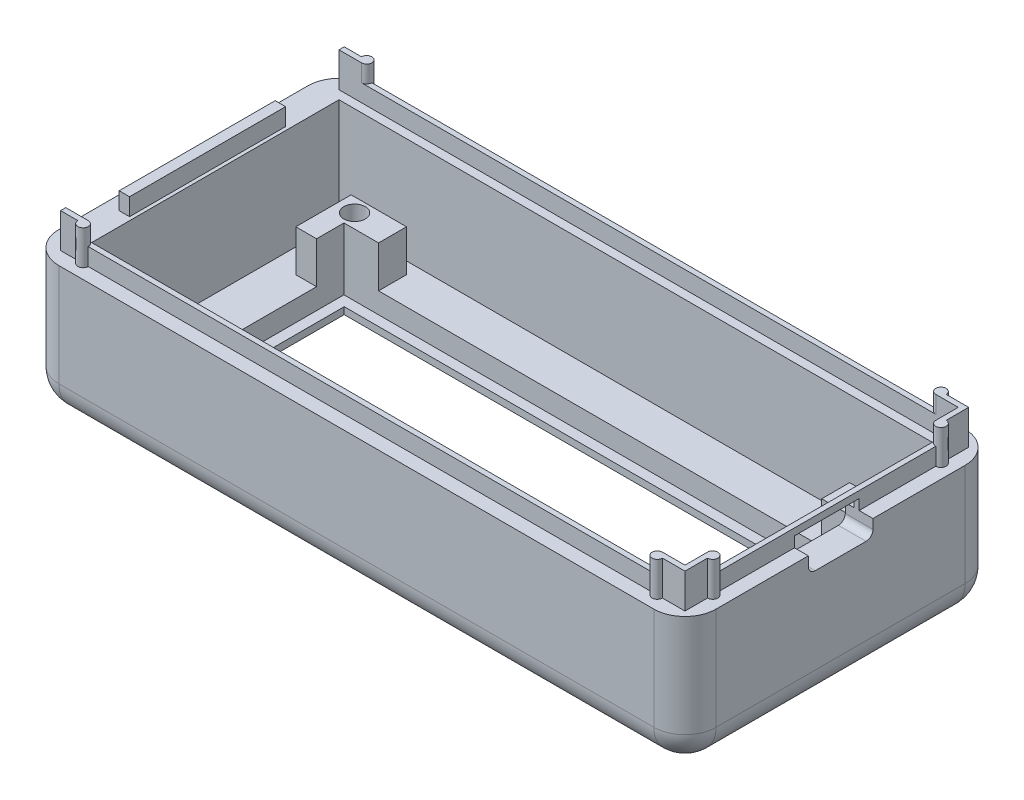
SolidWorks part; units mm, degrees
ref_plane "Спереди" through (0, 0, 0) normal (0, 0, 1) x (1, 0, 0)
ref_plane "Сверху" through (0, 0, 0) normal (0, 1, 0) x (1, 0, 0)
ref_plane "Справа" through (0, 0, 0) normal (1, 0, 0) x (0, 0, -1)
sketch "Эскиз1" plane through (0, 0, 0) normal (0, 1, 0) x (1, 0, 0)
  line L1 (0, 0) -> (95, 0)
  line L2 (0, 0) -> (0, -45)
  line L3 (0, -45) -> (95, -45)
  line L4 (95, 0) -> (95, -45)
  dimension "D1" = 45
  dimension "D2" = 95
extrude "Бобышка-Вытянуть1" add sketch "Эскиз1" along normal blind 19.3
shell "Оболочка1" thickness 4 removed face at (47.5, 19.3, 22.5)
fillet "Скругление1" radius 4.5 8 edges at (47.5, 0, 45) (95, 0, 22.5) (47.5, 0, 0) (0, 0, 22.5) (95, 9.65, 0) (95, 9.65, 45) (0, 9.65, 0) (0, 9.65, 45)
sketch "Эскиз2" plane through (0, 0, 0) normal (0, -1, 0) x (-1, 0, 0)
  line L0 (-47.5, -4.5) -> (-47.5, -40.5) construction
  line L1 (-83.025, -11.225) -> (-11.975, -11.225)
  line L2 (-83.025, -11.225) -> (-83.025, -33.775)
  line L3 (-83.025, -33.775) -> (-11.975, -33.775)
  line L4 (-11.975, -11.225) -> (-11.975, -33.775)
  line L5 (-4.5, -4.5) -> (-90.5, -4.5) construction
  line L6 (-90.5, -40.5) -> (-4.5, -40.5) construction
  line L7 (-90.5, -22.5) -> (-4.5, -22.5) construction
  line L8 (-90.5, -4.5) -> (-90.5, -40.5) construction
  line L9 (-4.5, -40.5) -> (-4.5, -4.5) construction
  point P17 (-83.025, -22.5)
  point P19 (-47.5, -33.775)
  dimension "D1" = 71.05
  dimension "D2" = 22.55
extrude "Вырез-Вытянуть1" cut sketch "Эскиз2" against normal blind 4.5
sketch "Эскиз6" plane through (0, 4, 0) normal (0, 1, 0) x (1, 0, 0)
  line L0 (11.975, -11.225) -> (11.975, -13.725)
  line L1 (11.975, -11.225) -> (11.975, -33.775) construction
  line L2 (11.975, -13.725) -> (7.475, -13.725)
  line L3 (7.475, -13.725) -> (7.475, -5.725)
  line L4 (7.475, -5.725) -> (15.475, -5.725)
  line L5 (15.475, -5.725) -> (15.475, -11.225)
  line L6 (83.025, -11.225) -> (11.975, -11.225) construction
  line L7 (15.475, -11.225) -> (11.975, -11.225)
  line L8 (11.975, -33.775) -> (11.975, -31.775)
  line L9 (11.975, -31.775) -> (7.475, -31.775)
  line L10 (7.475, -31.775) -> (7.475, -40.725)
  line L11 (7.475, -40.725) -> (15.475, -40.725)
  line L12 (15.475, -40.725) -> (15.475, -33.775)
  line L13 (11.975, -33.775) -> (83.025, -33.775) construction
  line L14 (15.475, -33.775) -> (11.975, -33.775)
  line L15 (47.5, -11.225) -> (47.5, -33.775) construction
  line L16 (11.975, -22.5) -> (83.025, -22.5) construction
  line L17 (83.025, -33.775) -> (83.025, -11.225) construction
  line L18 (87.525, -40.725) -> (79.525, -40.725)
  line L19 (79.525, -40.725) -> (79.525, -33.775)
  line L20 (79.525, -33.775) -> (83.025, -33.775)
  line L21 (83.025, -33.775) -> (83.025, -31.775)
  line L22 (83.025, -31.775) -> (87.525, -31.775)
  line L23 (87.525, -31.775) -> (87.525, -40.725)
  line L24 (79.525, -5.725) -> (79.525, -11.225)
  line L25 (79.525, -11.225) -> (83.025, -11.225)
  line L26 (83.025, -11.225) -> (83.025, -13.725)
  line L27 (83.025, -13.725) -> (87.525, -13.725)
  line L28 (87.525, -13.725) -> (87.525, -5.725)
  line L29 (87.525, -5.725) -> (79.525, -5.725)
  dimension "D1" = 8
  dimension "D2" = 8
  dimension "D3" = 4.5
  dimension "D4" = 4.5
  dimension "D5" = 35
  dimension "D6" = 8
  dimension "D7" = 2
  dimension "D8" = 5.5
extrude "Бобышка-Вытянуть3" add sketch "Эскиз6" along normal blind 6
sketch "Эскиз7" plane through (0, 10, 0) normal (0, 1, 0) x (1, 0, 0)
  line L2 (47.5, -11.225) -> (47.5, -33.775) construction
  line L3 (79.525, -11.225) -> (15.475, -11.225) construction
  line L4 (15.475, -33.775) -> (79.525, -33.775) construction
  line L5 (11.975, -22.75) -> (83.025, -22.75) construction
  line L6 (11.975, -13.725) -> (11.975, -31.775) construction
  line L7 (83.025, -31.775) -> (83.025, -13.725) construction
  line L10 (11.975, -13.725) -> (11.975, -11.225) construction
  line L11 (11.975, -11.225) -> (15.475, -11.225) construction
  line L12 (11.975, -31.775) -> (7.475, -31.775) construction
  line L13 (11.975, -33.775) -> (11.975, -31.775) construction
  circle A0 centre (9.975, -7.725) radius 1.55
  circle A1 centre (85.025, -7.725) radius 1.55
  circle A2 centre (9.975, -38.725) radius 1.55
  circle A3 centre (85.025, -38.725) radius 1.55
  point P28 (11.975, -32.775)
  dimension "D1" = 3.1
  dimension "D4" = 3.1
  dimension "D2" = 3.5
  dimension "D3" = 2
  dimension "D5" = 6.95
  dimension "D6" = 2
extrude "Вырез-Вытянуть2" cut sketch "Эскиз7" against normal blind 4
sketch "Эскиз8" plane through (0, 19.3, 0) normal (0, 1, 0) x (1, 0, 0)
  line L0 (91, -4) -> (4, -4) construction
  line L1 (2, -5.25) -> (2, -2)
  line L2 (4, -4) -> (4, -41) construction
  line L3 (47.5, -4) -> (47.5, -41) construction
  line L4 (91, -4) -> (4, -4) construction
  line L5 (4, -41) -> (91, -41) construction
  line L6 (4, -22.5) -> (91, -22.5) construction
  line L7 (4, -4) -> (4, -41) construction
  line L8 (91, -41) -> (91, -4) construction
  line L9 (2, -2) -> (5.25, -2)
  line L10 (2.75, -6) -> (2.75, -2.75)
  line L11 (2.75, -2.75) -> (6, -2.75)
  line L12 (92.25, -6) -> (92.25, -2.75)
  line L13 (92.25, -2.75) -> (89, -2.75)
  line L14 (93, -2) -> (89.75, -2)
  line L15 (93, -5.25) -> (93, -2)
  line L16 (93, -39.75) -> (93, -43)
  line L17 (93, -43) -> (89.75, -43)
  line L18 (92.25, -42.25) -> (89, -42.25)
  line L19 (92.25, -39) -> (92.25, -42.25)
  line L20 (2.75, -42.25) -> (6, -42.25)
  line L21 (2.75, -39) -> (2.75, -42.25)
  line L22 (2, -43) -> (5.25, -43)
  line L23 (2, -39.75) -> (2, -43)
  line L24 (2, -6.75) -> (2, -38.25)
  line L25 (2.75, -39) -> (2.75, -6)
  line L26 (6.75, -2) -> (88.25, -2)
  line L27 (89, -2.75) -> (6, -2.75)
  line L28 (92.25, -39) -> (92.25, -6)
  line L29 (93, -6.75) -> (93, -38.25)
  line L30 (89, -42.25) -> (6, -42.25)
  line L31 (6.75, -43) -> (88.25, -43)
  line L32 (2.75, -2.75) -> (2.75, -2)
  line L33 (2.75, -42.25) -> (2.75, -43)
  circle A0 centre (2, -6) radius 0.75
  circle A1 centre (6, -2) radius 0.75
  circle A2 centre (89, -2) radius 0.75
  circle A3 centre (93, -6) radius 0.75
  circle A4 centre (93, -39) radius 0.75
  circle A5 centre (89, -43) radius 0.75
  circle A6 centre (6, -43) radius 0.75
  circle A7 centre (2, -39) radius 0.75
  dimension "D1" = 1.5
  dimension "D4" = 1.5
  dimension "D2" = 2
  dimension "D3" = 2
  dimension "D5" = 2
  dimension "D6" = 2
extrude "Бобышка-Вытянуть5" add sketch "Эскиз8" along normal blind 5 contours A6 | A1 | A2 | L12 A3 L15 L14 A2 L13 | A3 | A4 | A5 L17 L16 A4 L19 L18 | A5 | L22 A6 L20 L33 | A1 L9 L32 L11 region at (4.0857, 19.3, 2.3875) region at (6, 19.3, 2) region at (4.0857, 19.3, 42.6125) region at (89.5703, 19.3, 2.5703) region at (89, 19.3, 2) region at (6, 19.3, 43) region at (90.625, 19.3, 42.3066) region at (89, 19.3, 43) region at (93, 19.3, 6) region at (93, 19.3, 39)
extrude "Бобышка-Вытянуть6" add sketch "Эскиз8<4>" along normal blind 2.5 contours L27 A2 L26 A1 | A4 L29 A3 L28 | L30 A6 L31 A5 region at (47.5, 19.3, 2.3758) region at (47.5, 19.3, 42.6242) region at (92.6229, 19.3, 22.5)
sketch "Эскиз8<4>" plane through (0, 19.3, 0) normal (0, 1, 0) x (1, 0, 0) same geometry as "Эскиз8"
sketch "Эскиз9" plane through (0, 19.3, 0) normal (0, 1, 0) x (1, 0, 0)
  line L0 (0, -4.5) -> (0, -40.5) construction
  line L1 (2, -11.225) -> (3.5, -11.225)
  line L2 (2, -11.225) -> (2, -33.775)
  line L3 (2, -33.775) -> (3.5, -33.775)
  line L4 (3.5, -11.225) -> (3.5, -33.775)
  line L5 (79.525, -11.225) -> (15.475, -11.225) construction
  line L6 (15.475, -33.775) -> (79.525, -33.775) construction
  dimension "D1" = 2
  dimension "D2" = 1.5
extrude "Бобышка-Вытянуть7" add sketch "Эскиз9" along normal blind 2.5
sketch "Эскиз10" plane through (0, 10, 0) normal (0, 1, 0) x (1, 0, 0)
  line L0 (87.525, -13.725) -> (87.525, -5.725) construction
  line L1 (10.475, -9.7624) -> (84.525, -9.7624)
  line L2 (10.475, -9.7624) -> (10.475, -36.725)
  line L3 (10.475, -36.725) -> (84.525, -36.725)
  line L4 (84.525, -9.7624) -> (84.525, -36.725)
  line L5 (79.525, -40.725) -> (87.525, -40.725) construction
  line L6 (79.525, -11.225) -> (83.025, -11.225) construction
  line L7 (7.475, -5.725) -> (7.475, -13.725) construction
  dimension "D1" = 3
  dimension "D2" = 4
  dimension "D3" = 1.4626
  dimension "D4" = 3
extrude "Вырез-Вытянуть3" cut sketch "Эскиз10" against normal blind 9
sketch "Эскиз12" plane through (95, 0, 0) normal (1, 0, 0) x (0, 0, -1)
  line L0 (-22.5, 19.3) -> (-22.5, 4.5) construction
  line L1 (-40.5, 19.3) -> (-4.5, 19.3) construction
  line L2 (-40.5, 4.5) -> (-4.5, 4.5) construction
  line L4 (-27.17, 19.3) -> (-17.83, 19.3)
  line L5 (-27.17, 19.3) -> (-27.17, 16.94)
  line L6 (-27.17, 16.94) -> (-17.83, 16.94)
  line L7 (-17.83, 19.3) -> (-17.83, 16.94)
  line L8 (-27.17, 19.3) -> (-17.83, 19.3)
  line L9 (-27.17, 19.3) -> (-27.17, 20.8)
  line L10 (-27.17, 20.8) -> (-17.83, 20.8)
  line L11 (-17.83, 19.3) -> (-17.83, 20.8)
  point P14 (0, 0)
  line M6 (-4.5, 19.3) -> (-40.5, 19.3)
  dimension "D1" = 2.36
  dimension "D2" = 4.67
  dimension "D3" = 4.67
  dimension "D4" = 1.5
extrude "Вырез-Вытянуть4" cut sketch "Эскиз12" against normal blind 24 contours L0 L8 L5 L6 | L0 L6 L7 M6 | L11 L10 L9 L8 M6 region at (95, 18.12, 20.165) region at (95, 18.12, 24.835) region at (95, 20.05, 22.5)
fillet "Скругление2" radius 1 1 edges at (93, 16.94, 27.17) type face fillet first side face at (93, 16.94, 22.5) second side face at (92.8125, 19.085, 27.17)
fillet "Скругление3" radius 1 1 edges at (93, 16.94, 17.83) type face fillet first side face at (92.8125, 19.085, 17.83) second side face at (93, 16.94, 22)
